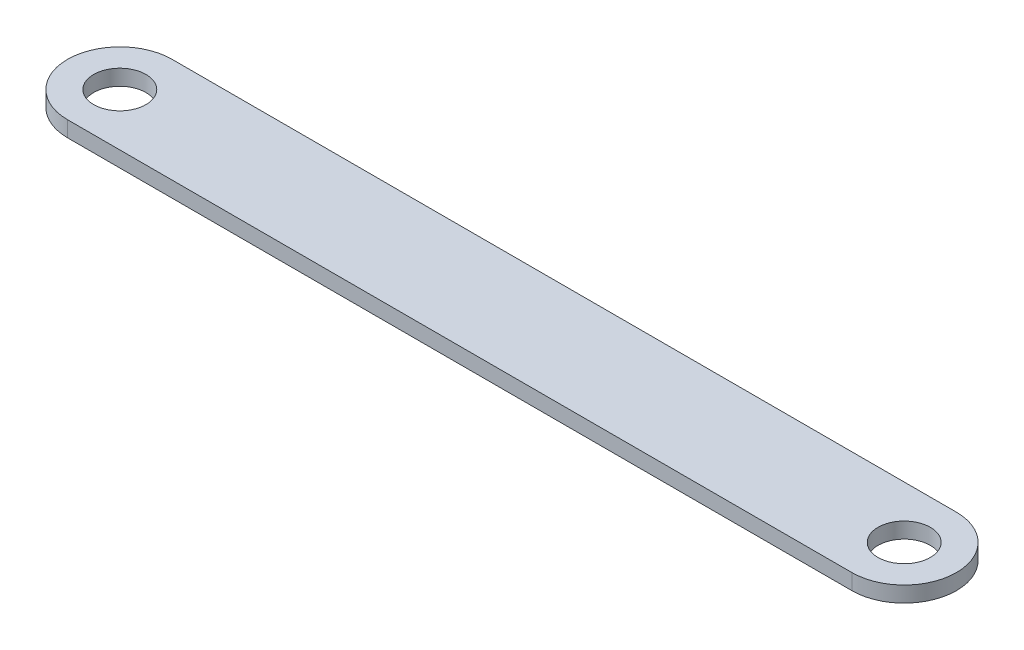
SolidWorks part; units mm, degrees
ref_plane "前视基准面" through (0, 0, 0) normal (0, 0, 1) x (1, 0, 0)
ref_plane "上视基准面" through (0, 0, 0) normal (0, 1, 0) x (1, 0, 0)
ref_plane "右视基准面" through (0, 0, 0) normal (1, 0, 0) x (0, 0, -1)
other "Configuration Table"
sketch "草图1" plane through (0, 0, 0) normal (0, 1, 0) x (1, 0, 0)
  line L0 (0, 0) -> (150, 0) construction
  line L1 (0, 10) -> (150, 10)
  line L2 (0, -10) -> (150, -10)
  arc A0 (0, 10) -> (0, -10) centre (0, 0) ccw
  arc A1 (150, -10) -> (150, 10) centre (150, 0) ccw
  circle A2 centre (0, 0) radius 5
  circle A3 centre (150, 0) radius 5
  point P3 (75, 0)
  point P12 (384.7579, 0)
  point P13 (207.6215, 0)
  dimension "D1" = 10
  dimension "D2" = 10
  dimension "D3" = 10
  dimension "D4" = 150
extrude "凸台-拉伸1" add sketch "草图1" along normal blind 3
